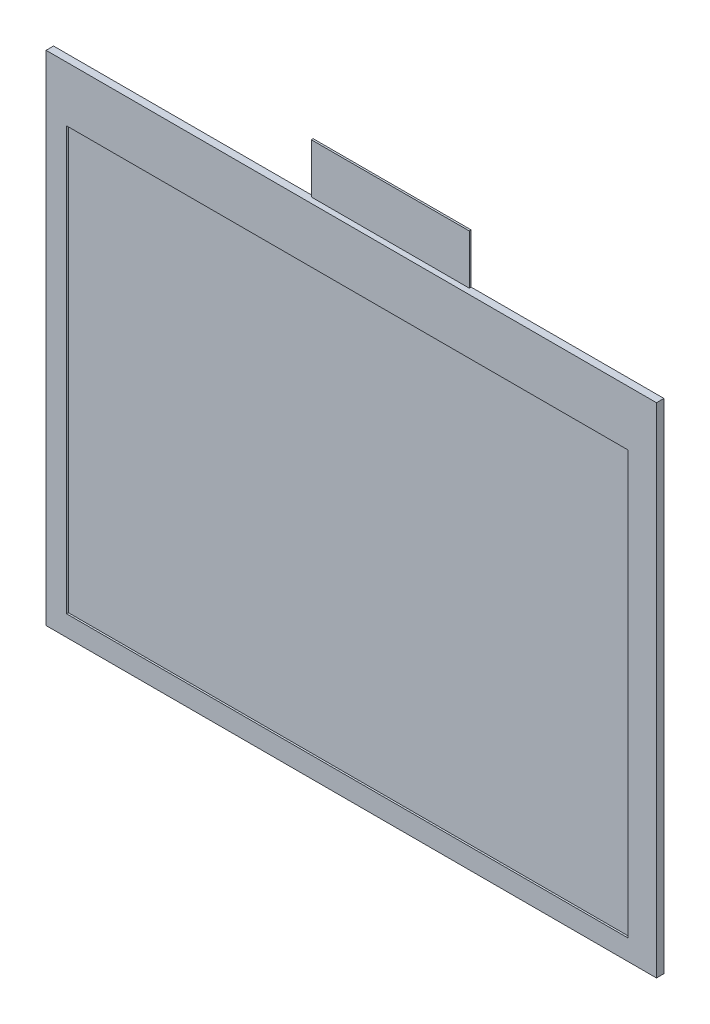
SolidWorks part; units mm, degrees
material "Corrugated Paper"
ref_plane "Front Plane" through (0, 0, 0) normal (0, 0, 1) x (1, 0, 0)
ref_plane "Top Plane" through (0, 0, 0) normal (0, 1, 0) x (1, 0, 0)
ref_plane "Right Plane" through (0, 0, 0) normal (1, 0, 0) x (0, 0, -1)
sketch "Sketch1" plane through (0, 0, 0) normal (0, 0, 1) x (1, 0, 0)
  line L0 (0, 41.849) -> (0, -44.3508) construction
  line L1 (-45.3, -34.1) -> (45.3, -34.1)
  line L2 (-45.3, -34.1) -> (-45.3, 34.1)
  line L3 (-45.3, 34.1) -> (45.3, 34.1)
  line L4 (45.3, -34.1) -> (45.3, 34.1)
  line L5 (-45.3, -34.1) -> (45.3, 34.1) construction
  line L6 (-45.3, 34.1) -> (45.3, -34.1) construction
  line L7 (-56.4252, 0) -> (58.6223, 0) construction
  line L9 (-48.6, -37.4) -> (49.9, -37.4)
  line L10 (-48.6, -37.4) -> (-48.6, 43)
  line L11 (-48.6, 43) -> (49.9, 43)
  line L12 (49.9, -37.4) -> (49.9, 43)
  line L13 (18.8, 43) -> (-6.7, 43)
  line L14 (18.8, 43) -> (18.8, 51)
  line L15 (18.8, 51) -> (-6.7, 51)
  line L16 (-6.7, 43) -> (-6.7, 51)
  point P0 (0, 0)
  dimension "D1" = 90.6
  dimension "D2" = 68.2
  dimension "D3" = 3.3
  dimension "D4" = 3.3
  dimension "D5" = 80.4
  dimension "D6" = 98.5
  dimension "D7" = 25.5
  dimension "D8" = 31.1
  dimension "D9" = 8
extrude "Boss-Extrude1" add sketch "Sketch1" along normal blind 1.2 contours L9 L12 L11 L10 L4 L1 L2 L3 region at (-47.3285, 2.8, 0)
extrude "Boss-Extrude2" add sketch "Sketch1<3>" along normal blind 0.9 contours L1 L4 L3 L2 region at (0, 0, 0)
sketch "Sketch1<3>" plane through (0, 0, 0) normal (0, 0, 1) x (1, 0, 0) same geometry as "Sketch1"
extrude "Boss-Extrude3" add sketch "Sketch1<4>" along normal blind 0.3 contours L16 L11 L14 L15 region at (6.05, 47, 0)
sketch "Sketch1<4>" plane through (0, 0, 0) normal (0, 0, 1) x (1, 0, 0) same geometry as "Sketch1"
